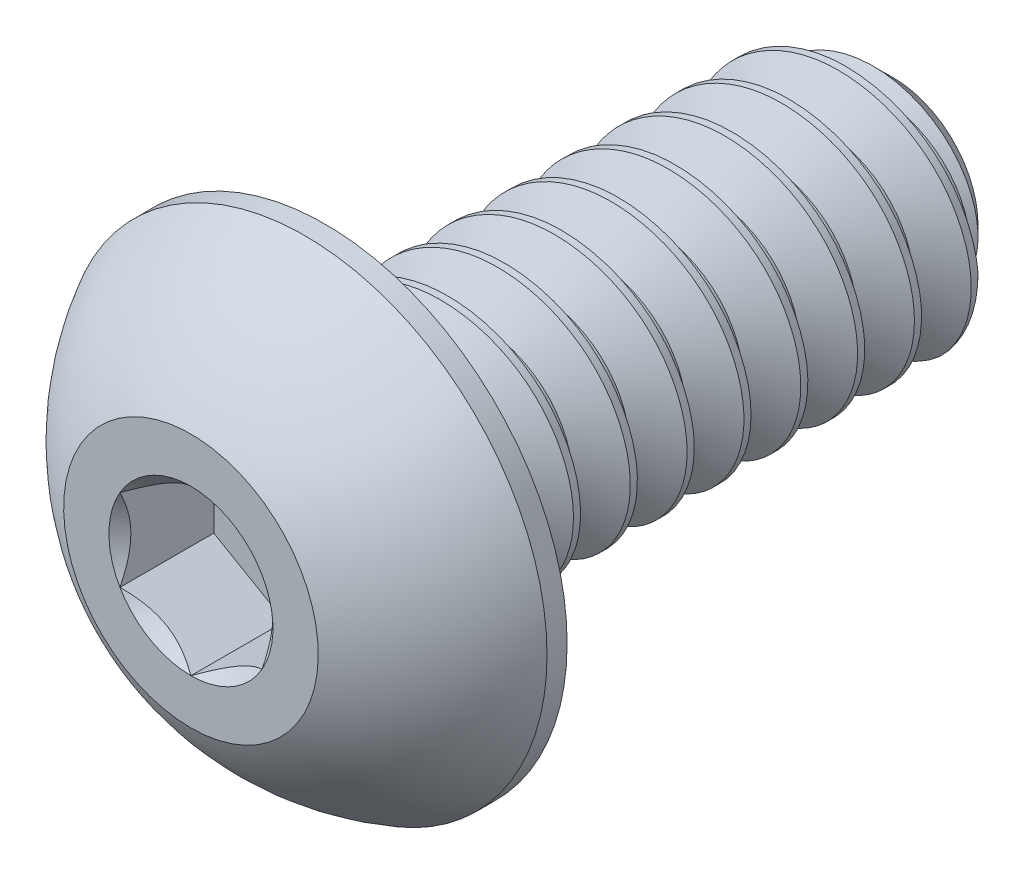
SolidWorks part; units mm, degrees
ref_plane "Front" through (0, 0, 0) normal (0, 0, 1) x (1, 0, 0)
ref_plane "Top" through (0, 0, 0) normal (0, 1, 0) x (1, 0, 0)
ref_plane "Right" through (0, 0, 0) normal (1, 0, 0) x (0, 0, -1)
sketch "Sketch1" plane through (0, 0, 0) normal (1, 0, 0) x (0, 0, -1)
  line L2 (1.4986, 1.4224) -> (7.8486, 1.4224)
  line L3 (7.8486, 1.4224) -> (7.8486, 0)
  line L4 (7.8486, 0) -> (1.4986, 0)
  line L6 (1.2738, 2.7051) -> (1.4986, 2.7051) construction
  line L7 (7.8486, 1.4224) -> (7.8486, -1.4224) construction
  line L8 (0, 0) -> (1.4986, 0) construction
  line L9 (1.4986, 2.7051) -> (1.4986, -2.7051) construction
  line L11 (1.4986, 1.4224) -> (1.4986, 0)
  line L13 (0, 0.7937) -> (0, -0.7937) construction
  line L14 (0, 0.7937) -> (0, 1.4224) construction
  arc A3 (0, 1.4224) -> (1.2738, 2.7051) centre (2.7151, 0) cw construction
  dimension "D1" = 0.2248
  dimension "Head Ht" = 1.4986
  dimension "Head Dia" = 5.4102
  dimension "Dia" = 2.8448
  dimension "Lg" = 6.35
  dimension "Hex" = 1.5875
revolve "Revolve1" add sketch "Sketch1" angle 360 mid plane about L4
sketch "Sketch3" plane through (0, 0, -7.8486) normal (0, 0, -1) x (-1, 0, 0)
  circle A0 centre (0, 0) radius 1.4224
curve "Helix/Spiral1" pitch 0.635 height 7.8486 radius 1.4224 centre (0, 0, -7.8486) axis (0, 0, 1) start towards (0, 1, 0)
sketch "Sketch2" plane through (0, 0, 0) normal (1, 0, 0) x (0, 0, -1)
  line L0 (7.8486, 1.4224) -> (8.4042, 1.4224)
  line L1 (8.4042, 1.4224) -> (8.1661, 1.01)
  line L2 (8.1661, 1.01) -> (8.0867, 1.01)
  line L3 (8.0867, 1.01) -> (7.8486, 1.4224)
  line L4 (7.9677, 1.2162) -> (8.2852, 1.2162) construction
  dimension "D1" = 60
  dimension "D2" = 0.0794
  dimension "D3" = 0.3175
chamfer "Chamfer1" distance 0.4763 angle 45 1 edges at (0, 1.4224, -7.8486)
sweep "Cut-Sweep1" cut profiles "Sketch2" path "Helix/Spiral1"
sketch "Sketch7" plane through (0, 0, 0) normal (1, 0, 0) x (0, 0, -1)
  line L6 (1.2738, 2.7051) -> (1.4986, 2.7051) construction
  line L8 (0, 0) -> (1.4986, 0) construction
  line L11 (1.4986, 2.7051) -> (1.4986, -2.7051) construction
  line L12 (1.2738, 2.7051) -> (1.4986, 2.7051)
  line L13 (0, 0) -> (1.4986, 0)
  line L14 (0, 0.7937) -> (0, -0.7937) construction
  line L15 (1.4986, 2.7051) -> (1.4986, 0)
  line L16 (0, 1.4224) -> (0, 0)
  arc A2 (1.2738, 2.7051) -> (0, 1.4224) centre (2.7151, 0) ccw construction
  arc A3 (1.2738, 2.7051) -> (0, 1.4224) centre (2.7151, 0) ccw
revolve "Revolve2" add sketch "Sketch7" angle 360 mid plane about L13
sketch "Sketch5" plane through (0, 0, 0) normal (0, 0, 1) x (1, 0, 0)
  line L1 (0.7937, -0.4583) -> (0.7937, 0.4583)
  line L2 (0.7937, 0.4583) -> (0, 0.9165)
  line L3 (0, 0.9165) -> (-0.7938, 0.4583)
  line L4 (-0.7938, 0.4583) -> (-0.7937, -0.4583)
  line L5 (-0.7937, -0.4583) -> (0, -0.9165)
  line L6 (0, -0.9165) -> (0.7937, -0.4583)
  circle A0 centre (0, 0) radius 0.7937 construction
extrude "Cut-Extrude2" cut sketch "Sketch5" against normal blind 1.049
sketch "Sketch6" plane through (0, 0, 0) normal (0, 0, 1) x (1, 0, 0)
  circle A0 centre (0, 0) radius 0.9165
extrude "Cut-Extrude3" cut sketch "Sketch6" against normal blind 1.049 draft 45
sketch "Sketch9" [suppressed] plane through (0, 0, -1.4986) normal (0, 0, 1) x (1, 0, 0)
  circle A2 centre (0, 0) radius 1.4224
extrude "Boss-Extrude2" [suppressed] add sketch "Sketch9" against normal offset from surface (6.35 mm away) 22.225 up to face at (0, 0.9462, -7.8486)
sketch "Sketch10" plane through (0, 0, 0) normal (1, 0, 0) x (0, 0, -1)
  line L0 (7.8486, 1.4224) -> (7.8486, -1.4224) construction
  point P0 (6.8961, -1.4224)
  dimension "D1" = 0.9525
equation "\"D3@Helix/Spiral1\" = \"Lg@Sketch1\" + \"Head Ht@Sketch1\""
equation "\"D2@Sketch2\" = \"D4@Helix/Spiral1\" * .125"
equation "\"D3@Sketch2\" = \"D4@Helix/Spiral1\" * .5"
equation "\"D1@Chamfer1\" = \"D4@Helix/Spiral1\" * .75"
equation "\"D1@Cut-Extrude2\" = \"Head Ht@Sketch1\" * .7"
equation "\"D1@Sketch1\" = \"Head Ht@Sketch1\" * .15"
equation "\"D1@Sketch10\" = \"D4@Helix/Spiral1\" * 1.5"
equation "\"D1@Cut-Extrude3\" = \"D1@Cut-Extrude2\""
